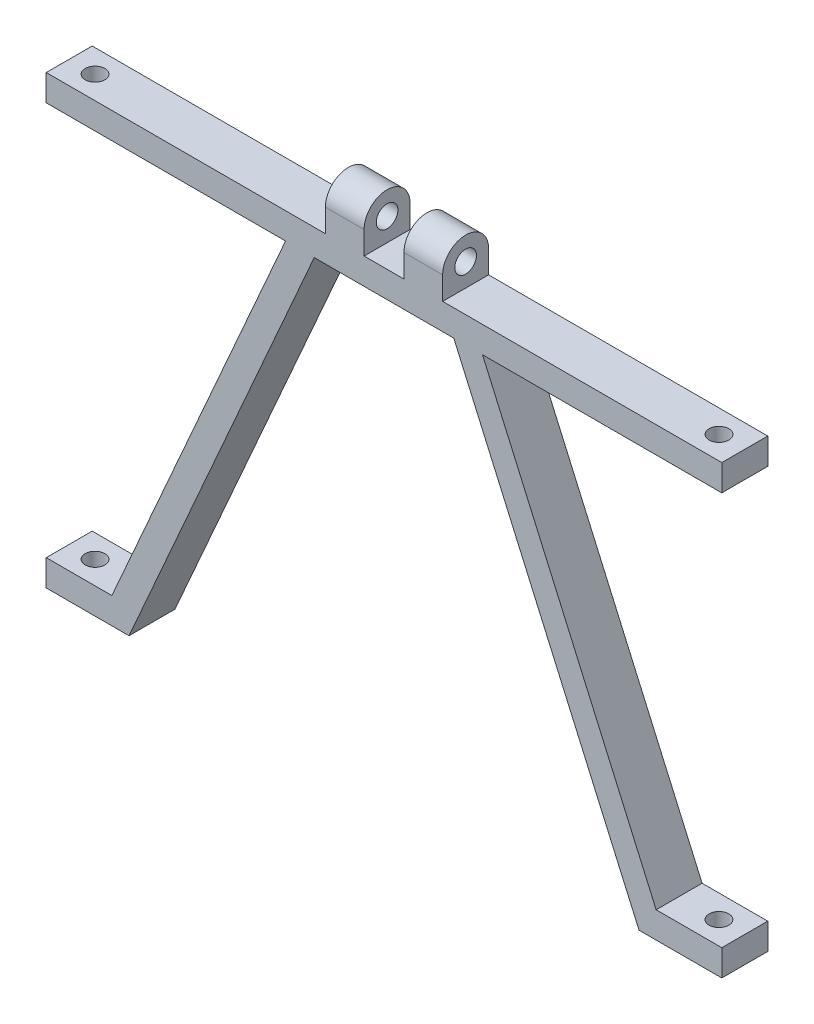
SolidWorks part; units mm, degrees
ref_plane "Front Plane" through (0, 0, 0) normal (0, 0, 1) x (1, 0, 0)
ref_plane "Top Plane" through (0, 0, 0) normal (0, 1, 0) x (1, 0, 0)
ref_plane "Right Plane" through (0, 0, 0) normal (1, 0, 0) x (0, 0, -1)
sketch "Croquis4" plane through (0, 0, 0) normal (0, 0, 1) x (1, 0, 0)
  line L0 (51.455, 0) -> (-51.455, 0)
  line L1 (51.455, -4) -> (-51.455, -4)
  line L2 (-51.455, -4) -> (-51.455, 0)
  line L3 (51.455, -4) -> (51.455, 0)
  line L4 (-15, -4) -> (-41.455, -64)
  line L5 (-41.455, -64) -> (-51.455, -64)
  line L6 (-51.455, -64) -> (-51.455, -68)
  line L7 (-51.455, -68) -> (-38.8471, -68)
  line L8 (-38.8471, -68) -> (-10.6284, -4)
  line L9 (0, 0) -> (0, -4) construction
  line L10 (15, -4) -> (41.455, -64)
  line L11 (38.8471, -68) -> (10.6284, -4)
  line L12 (51.455, -68) -> (38.8471, -68)
  line L13 (51.455, -64) -> (51.455, -68)
  line L14 (41.455, -64) -> (51.455, -64)
  point P4 (0, 0)
  dimension "D1" = 102.91
  dimension "D3" = 4
  dimension "D4" = 4
  dimension "D5" = 60
  dimension "D6" = 15
  dimension "D7" = 10
  dimension "D2" = 4
extrude "Saliente-Extruir3" add sketch "Croquis4" along normal blind 7 contours L7 L8 L1 L4 L5 L6 | L9 L0 L2 L1 | L0 L9 L1 L3 | L14 L10 L1 L11 L12 L13 region at (25.7275, -2, 0) region at (-25.7275, -2, 0) region at (29.2253, -39.4524, 0) region at (-29.2253, -39.4524, 0)
sketch "Croquis5" plane through (0, 0, 0) normal (0, 1, 0) x (1, 0, 0)
  line L0 (-51.455, -7) -> (-51.455, 0) construction
  circle A0 centre (-47.525, -3.5) radius 1.5
  circle A1 centre (47.525, -3.5) radius 1.5
  point P8 (-51.455, -3.5)
  dimension "D3" = 3
  dimension "D1" = 95.05
  dimension "D2" = 47.525
extrude "Cortar-Extruir2" cut sketch "Croquis5" against normal through all and the other way through all
sketch "Croquis6" plane through (0, 0, 0) normal (1, 0, 0) x (0, 0, -1)
  line L0 (-7, 0) -> (0, 0) construction
  line L1 (-3.5, 3.5) -> (0, 3.5) construction
  line L3 (-7, 3.5) -> (-7, 0)
  line L4 (-7, 0) -> (0, 0)
  line L5 (0, 0) -> (0, 3.5)
  circle A0 centre (-3.5, 3.5) radius 3.5
  circle A1 centre (-3.5, 3.5) radius 1.65
  dimension "D1" = 7
  dimension "D2" = 3.3
extrude "Saliente-Extruir4" add sketch "Croquis6" along normal mid plane 30 contours A1 A0 | A0 L3 L4 | A0 L4 L5 region at (0, 0.7818, 6.2182) region at (0, 6.901, 3.5) region at (0, 0.7818, 0.7818)
sketch "Croquis7" plane through (0, 0, 7) normal (0, 0, 1) x (1, 0, 0)
  line L0 (15, 7) -> (-15, 7) construction
  line L1 (-15, 0) -> (-8.93, 0)
  line L2 (-15, 0) -> (-15, 7)
  line L3 (-15, 7) -> (-8.93, 7)
  line L4 (-8.93, 0) -> (-8.93, 7)
  line L5 (-15, 7) -> (-15, 3.5) construction
  line L6 (-15, 0) -> (-51.455, 0) construction
  line L7 (15, 0) -> (8.93, 0)
  line L8 (15, 0) -> (15, 7)
  line L9 (15, 7) -> (8.93, 7)
  line L10 (8.93, 0) -> (8.93, 7)
  line L11 (-3.035, 0) -> (3.035, 0)
  line L12 (-3.035, 0) -> (-3.035, 7)
  line L13 (-3.035, 7) -> (3.035, 7)
  line L14 (3.035, 0) -> (3.035, 7)
  point P17 (0, 0)
  dimension "D1" = 6.07
  dimension "D2" = 6.07
  dimension "D3" = 6.07
extrude "Cortar-Extruir3" cut sketch "Croquis7" against normal through all
